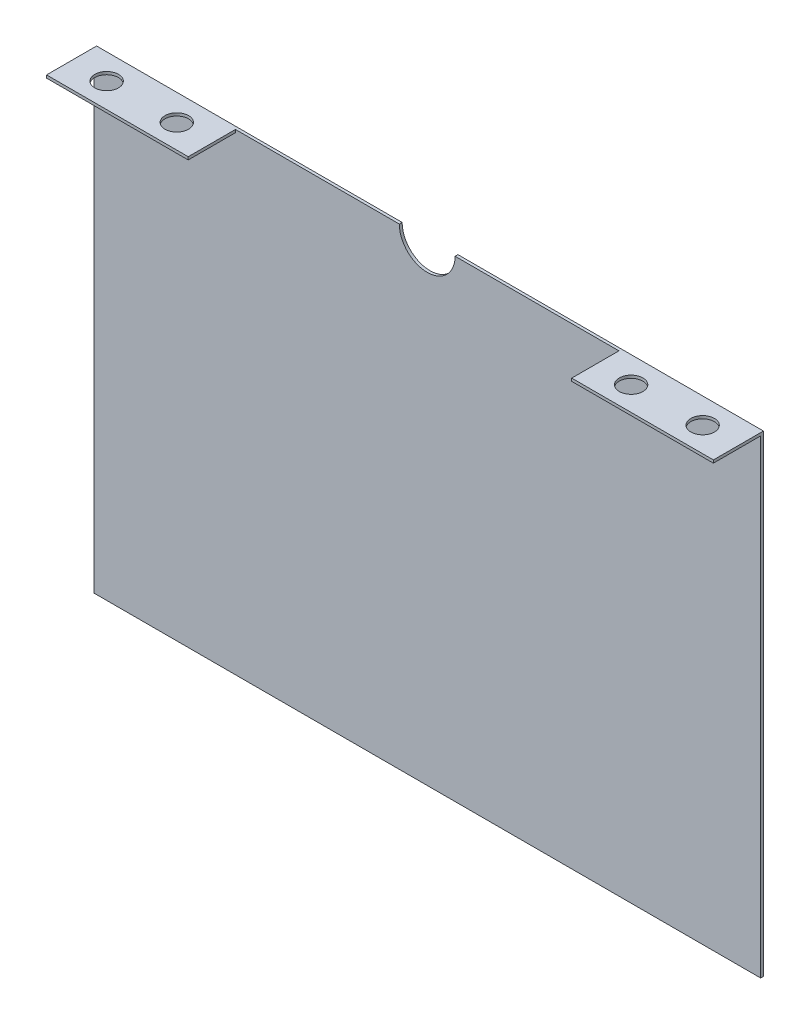
SolidWorks part; units mm, degrees
material "Plain Carbon Steel"
ref_plane "Front Plane" through (0, 0, 0) normal (0, 0, 1) x (1, 0, 0)
ref_plane "Top Plane" through (0, 0, 0) normal (0, 1, 0) x (1, 0, 0)
ref_plane "Right Plane" through (0, 0, 0) normal (1, 0, 0) x (0, 0, -1)
sketch "Sketch1" plane through (0, 0, 0) normal (0, 0, 1) x (1, 0, 0)
  line L0 (0, 0) -> (0, 177.8) construction
  line L1 (-179.3189, 177.8) -> (-15, 177.8)
  line L2 (-179.3189, 177.8) -> (-179.3189, -76.2)
  line L3 (-179.3189, -76.2) -> (179.3189, -76.2)
  line L4 (179.3189, 177.8) -> (179.3189, -76.2)
  line L5 (-179.3189, 0) -> (179.3189, 0) construction
  line L6 (15, 177.8) -> (179.3189, 177.8)
  line L7 (-15, 177.8) -> (15, 177.8) construction
  arc A0 (15, 177.8) -> (-15, 177.8) centre (0, 177.8) cw
  point P10 (0, 0)
  point P12 (0, 0)
  dimension "D3" = 15
  dimension "D1" = 358.6378
  dimension "D2" = 177.8
  dimension "D4" = 179.3189
  dimension "D5" = 76.2
extrude "Bottom Center Casing" add sketch "Sketch1" along normal blind 1.5189
sketch "Sketch2" plane through (0, 0, 1.5189) normal (0, 0, 1) x (1, 0, 0)
  line L0 (-15, 177.8) -> (-179.3189, 177.8) construction
  line L1 (179.3189, 177.8) -> (15, 177.8) construction
  line L2 (0, 177.8) -> (0, 144.5) construction
  line L3 (-97.1595, 177.8) -> (97.1595, 177.8) construction
  point P0 (-97.1595, 177.8)
  point P3 (-97.1595, 177.8)
  point P4 (97.1595, 177.8)
  point P7 (97.1595, 177.8)
  point P12 (0, 177.8)
  dimension "D1" = 33.3
sketch "Sketch3" plane through (0, 0, 1.5189) normal (0, 0, 1) x (1, 0, 0)
  line L1 (-179.3189, 177.8) -> (-103.1189, 177.8)
  line L2 (-179.3189, 177.8) -> (-179.3189, 176.2811)
  line L3 (-179.3189, 176.2811) -> (-103.1189, 176.2811)
  line L4 (-103.1189, 177.8) -> (-103.1189, 176.2811)
  line L5 (179.3189, 177.8) -> (103.1189, 177.8)
  line L6 (179.3189, 177.8) -> (179.3189, 176.2811)
  line L7 (179.3189, 176.2811) -> (103.1189, 176.2811)
  line L8 (103.1189, 177.8) -> (103.1189, 176.2811)
  dimension "D1" = 76.2
  dimension "D2" = 1.5189
  dimension "D3" = 1.5189
  dimension "D4" = 76.2
extrude "Boss-Extrude1" add sketch "Sketch3" along normal blind 25.4
sketch "Sketch4" plane through (0, 177.8, 0) normal (0, 1, 0) x (1, 0, 0)
  line L0 (-179.3189, -13.4595) -> (-103.1189, -14.2189) construction
  line L1 (-179.3189, -26.9189) -> (-179.3189, 0) construction
  line L2 (-103.1189, -26.9189) -> (-103.1189, -1.5189) construction
  line L4 (0, -55) -> (0, 55) construction
  circle A0 centre (-160.2689, -13.6493) radius 6.35
  circle A1 centre (-122.1689, -14.0291) radius 6.35
  circle A2 centre (122.1689, -14.0291) radius 6.35
  circle A3 centre (160.2689, -13.6493) radius 6.35
  dimension "D1" = 12.7
  dimension "D2" = 19.05
  dimension "D3" = 38.1
extrude "Cut-Extrude1" cut sketch "Sketch4" against normal blind 25.4
